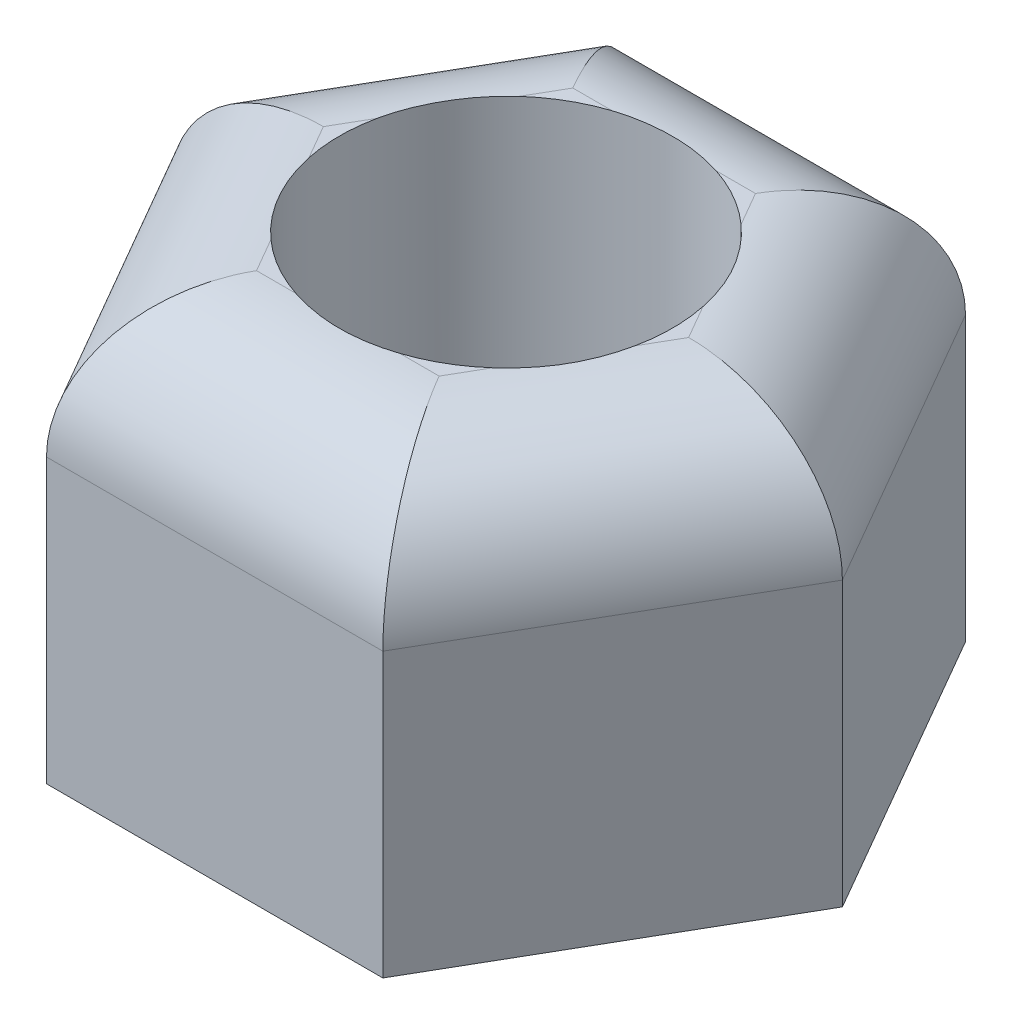
SolidWorks part; units mm, degrees
ref_plane "Front Plane" through (0, 0, 0) normal (0, 0, 1) x (1, 0, 0)
ref_plane "Top Plane" through (0, 0, 0) normal (0, 1, 0) x (1, 0, 0)
ref_plane "Right Plane" through (0, 0, 0) normal (1, 0, 0) x (0, 0, -1)
sketch "Sketch1" plane through (0, 0, 0) normal (0, 1, 0) x (1, 0, 0)
  line L1 (-6.4158, 0) -> (-3.2079, -5.5563)
  line L2 (-3.2079, -5.5563) -> (3.2079, -5.5562)
  line L3 (3.2079, -5.5562) -> (6.4158, 0)
  line L4 (6.4158, 0) -> (3.2079, 5.5563)
  line L5 (3.2079, 5.5563) -> (-3.2079, 5.5562)
  line L6 (-3.2079, 5.5562) -> (-6.4158, 0)
  circle A0 centre (0, 0) radius 5.5563 construction
  circle A1 centre (0, 0) radius 3.175
  dimension "D2" = 6.35
  dimension "D1" = 11.1125
extrude "Boss-Extrude1" add sketch "Sketch1" along normal blind 7.9375
fillet "Fillet1" radius 2.54 6 edges at (4.8119, 7.9375, 2.7781) (0, 7.9375, 5.5562) (-4.8119, 7.9375, 2.7781) (-4.8119, 7.9375, -2.7781) (0, 7.9375, -5.5563) (4.8119, 7.9375, -2.7781)
